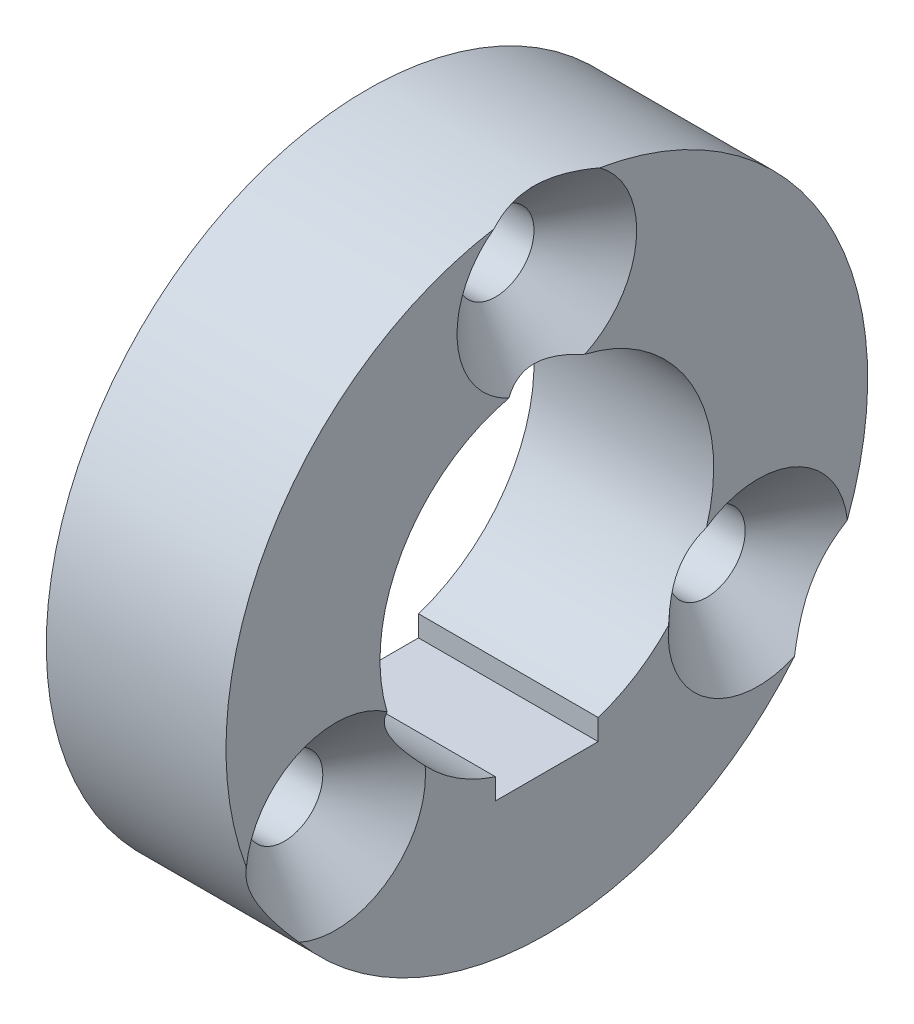
SolidWorks part; units mm, degrees
ref_plane "Front Plane" through (0, 0, 0) normal (0, 0, 1) x (1, 0, 0)
ref_plane "Top Plane" through (0, 0, 0) normal (0, 1, 0) x (1, 0, 0)
ref_plane "Right Plane" through (0, 0, 0) normal (1, 0, 0) x (0, 0, -1)
sketch "Sketch1" plane through (0, 0, 0) normal (1, 0, 0) x (0, 0, -1)
  line L0 (-8.2272, -4.75) -> (0, 9.5) construction
  line L1 (0, 9.5) -> (8.2272, -4.75) construction
  line L2 (8.2272, -4.75) -> (-8.2272, -4.75) construction
  line L3 (-8.2272, -4.75) -> (0, 0) construction
  line L4 (0, 0) -> (0, 9.5) construction
  line L5 (8.2272, -4.75) -> (0, 0) construction
  circle A0 centre (0, 0) radius 12.5
  circle A1 centre (0, 0) radius 6.5
  circle A2 centre (0, 9.5) radius 3 construction
  circle A3 centre (0, 9.5) radius 1.5
  circle A4 centre (-8.2272, -4.75) radius 1.5
  circle A5 centre (8.2272, -4.75) radius 1.5
  dimension "D1" = 25
  dimension "D2" = 13
  dimension "D3" = 6
  dimension "D4" = 3
extrude "Boss-Extrude1" add sketch "Sketch1" along normal blind 7
chamfer "Chamfer1" distance 2 angle 45 3 edges at (7, -4.75, -9.7272) (7, -4.75, 6.7272) (7, 9.5, -1.5)
sketch "Sketch2" plane through (0, 0, 0) normal (-1, 0, 0) x (0, 0, 1)
  line L0 (-2, -3) -> (-2, -7)
  line L1 (-2, -3) -> (2, -3)
  line L2 (-2, -7) -> (2, -7)
  line L3 (2, -3) -> (2, -7)
  line L4 (-2, -3) -> (2, -7) construction
  line L5 (-2, -7) -> (2, -3) construction
  line L6 (0, 0) -> (0, -5) construction
  circle A0 centre (0, 0) radius 5 construction
  point P1 (0, -5)
  dimension "D2" = 10
  dimension "D1" = 4
extrude "Cut-Extrude1" cut sketch "Sketch2" against normal blind 10
